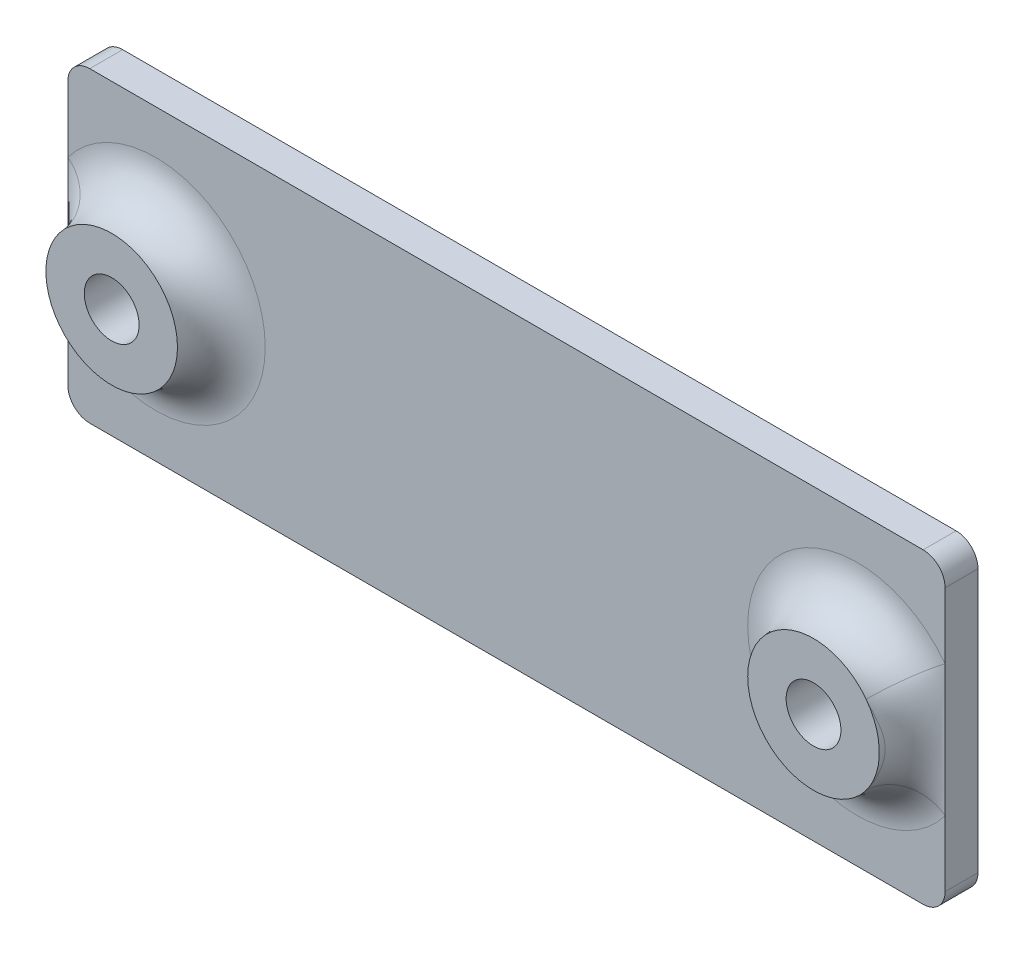
SolidWorks part; units mm, degrees
ref_plane "Front Plane" through (0, 0, 0) normal (0, 0, 1) x (1, 0, 0)
ref_plane "Top Plane" through (0, 0, 0) normal (0, 1, 0) x (1, 0, 0)
ref_plane "Right Plane" through (0, 0, 0) normal (1, 0, 0) x (0, 0, -1)
sketch "Sketch1" plane through (0, 0, 0) normal (0, 0, 1) x (1, 0, 0)
  line L1 (-21.6888, 7) -> (18.3112, 7)
  line L2 (-21.6888, 7) -> (-21.6888, -7)
  line L3 (-21.6888, -7) -> (18.3112, -7)
  line L4 (18.3112, 7) -> (18.3112, -7)
  dimension "D1" = 40
  dimension "D2" = 14
extrude "Boss-Extrude1" add sketch "Sketch1" along normal blind 1.5
sketch "Sketch2" plane through (0, 0, 1.5) normal (0, 0, 1) x (1, 0, 0)
  line L0 (18.3112, -7) -> (18.3112, 7) construction
  line L1 (-21.6888, -7) -> (18.3112, -7) construction
  line L2 (18.3112, 7) -> (-21.6888, 7) construction
  line L3 (-21.6888, 7) -> (-21.6888, -7) construction
  circle A0 centre (14.3112, 0) radius 1.25
  circle A1 centre (-17.6888, 0) radius 1.25
  circle A2 centre (-17.6888, 0) radius 3
  circle A3 centre (14.3112, 0) radius 3
  dimension "D3" = 2.5
  dimension "D6" = 2.5
  dimension "D7" = 6
  dimension "D8" = 6
  dimension "D1" = 4
  dimension "D2" = 7
  dimension "D4" = 7
  dimension "D5" = 4
extrude "Boss-Extrude2" add sketch "Sketch2" along normal blind 2
fillet "Fillet1" radius 2 2 edges at (17.3112, 0, 1.5) (-14.6888, 0, 1.5)
fillet "Fillet2" radius 1 4 edges at (-21.6888, 7, 0.75) (18.3112, 7, 0.75) (18.3112, -7, 0.75) (-21.6888, -7, 0.75)
extrude "Cut-Extrude1" cut sketch "Sketch2<2>" against normal blind 10 contours A1 | A0 region at (14.3112, 0, 1.5) region at (-17.6888, 0, 1.5)
sketch "Sketch2<2>" plane through (0, 0, 1.5) normal (0, 0, 1) x (1, 0, 0) same geometry as "Sketch2"
